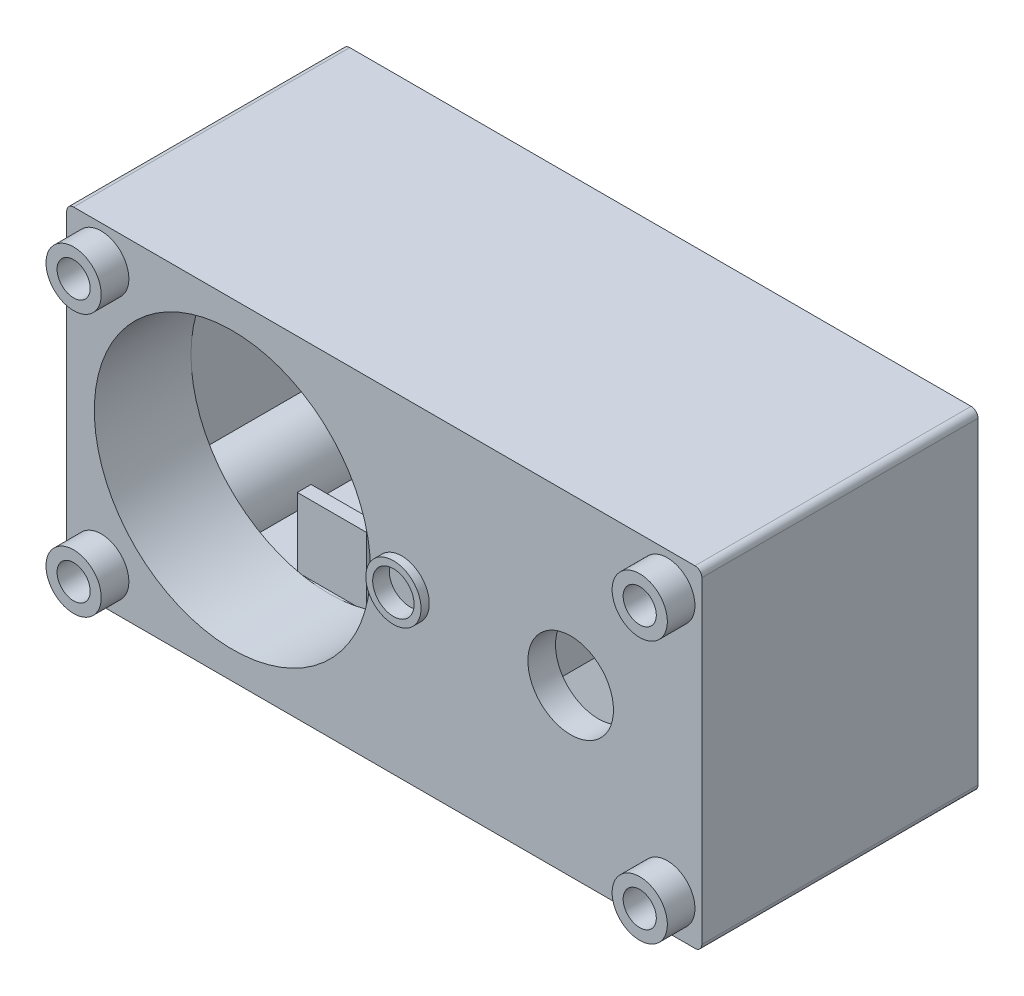
SolidWorks part; units mm, degrees
ref_plane "前视基准面" through (0, 0, 0) normal (0, 0, 1) x (1, 0, 0)
ref_plane "上视基准面" through (0, 0, 0) normal (0, 1, 0) x (1, 0, 0)
ref_plane "右视基准面" through (0, 0, 0) normal (1, 0, 0) x (0, 0, -1)
sketch "草图1" plane through (0, 0, 0) normal (0, 0, 1) x (1, 0, 0)
  line L0 (0, 0) -> (0, -8.3298) construction
  line L1 (-11.5, -6) -> (11.5, -6)
  line L2 (-11.5, -6) -> (-11.5, 6)
  line L3 (-11.5, 6) -> (11.5, 6)
  line L4 (11.5, -6) -> (11.5, 6)
  line L5 (-11.5, -6) -> (11.5, 6) construction
  line L6 (-11.5, 6) -> (11.5, -6) construction
  circle A0 centre (-10.25, 4.75) radius 0.6
  circle A1 centre (-10.25, -4.75) radius 0.6
  circle A2 centre (10.25, -4.75) radius 0.6
  circle A3 centre (10.25, 4.75) radius 0.6
  point P0 (0, 0)
  dimension "D3" = 1.2
  dimension "D1" = 23
  dimension "D2" = 12
  dimension "D4" = 1.25
  dimension "D5" = 1.25
  dimension "D6" = 1.25
extrude "凸台-拉伸1" add sketch "草图1" along normal blind 10 contours A0 | A1 | A3 | L1 L4 L3 L2 | A2 region at (-10.25, 4.75, 0) region at (-10.25, -4.75, 0) region at (10.25, 4.75, 0)
shell "抽壳2" thickness 1 removed face at (9.65, -4.75, 0)
extrude "拉伸-薄壁1" add sketch "草图1<3>" along normal blind 1 from offset 10 thin contours A0 | A1 | A2 | A3 thin type one direction wall 0.4
sketch "草图1<3>" plane through (0, 0, 0) normal (0, 0, 1) x (1, 0, 0) same geometry as "草图1"
sketch "草图2" plane through (0, 0, 10) normal (0, 0, 1) x (1, 0, 0)
  line L0 (11.5, -6) -> (11.5, 6) construction
  line L1 (-11.5, -6) -> (-11.5, 6) construction
  circle A0 centre (-5.5, 0) radius 5
  circle A1 centre (6.75, 0) radius 1.55
  circle A3 centre (0.63, 0) radius 0.75
  dimension "D1" = 3.1
  dimension "D3" = 10
  dimension "D5" = 1.5
  dimension "D2" = 4.75
  dimension "D4" = 6
  dimension "D6" = 6.13
extrude "切除-拉伸1" cut sketch "草图2" against normal up to next contours A0 | A1 region at (-5.5, 0, 10) region at (6.75, 0, 10)
extrude "拉伸-薄壁2" add sketch "草图2<3>" along normal blind 0.3 thin contours A3 thin type one direction wall 0.25
sketch "草图2<3>" plane through (0, 0, 10) normal (0, 0, 1) x (1, 0, 0) same geometry as "草图2"
extrude "切除-拉伸2" cut sketch "草图2<4>" against normal blind 0.3 contours A3
sketch "草图2<4>" plane through (0, 0, 10) normal (0, 0, 1) x (1, 0, 0) same geometry as "草图2"
sketch "草图3" plane through (0, 0, 9) normal (0, 0, -1) x (-1, 0, 0)
  line L0 (-4.575, 5) -> (-2.95, 3.375)
  line L1 (8.6697, 5) -> (-8.6697, 5) construction
  line L2 (-2.95, 3.375) -> (-2.95, -3.375)
  line L3 (-2.95, -3.375) -> (-4.575, -5)
  line L4 (5.5, -5) -> (-8.6697, -5) construction
  line L5 (-10.5, -3.1697) -> (-10.5, 3.1697) construction
  dimension "D1" = 7.55
  dimension "D2" = 135
  dimension "D3" = 135
  dimension "D4" = 6.75
extrude "拉伸-薄壁3" add sketch "草图3" along normal blind 5 thin thin type one direction reverse wall 0.5
sketch "草图4" plane through (0, 0, 9) normal (0, 0, -1) x (-1, 0, 0)
  circle A0 centre (5.5, 0) radius 5 construction
  circle A1 centre (5.5, 0) radius 5
extrude "拉伸-薄壁4" add sketch "草图4" along normal blind 2.5 thin thin type one direction wall 0.5
sketch "草图5" plane through (0, 0, 10) normal (0, 0, 1) x (1, 0, 0)
  line L0 (-5.5, 5) -> (-7.7913, 5) construction
  line L1 (-6.75, 5) -> (-4.25, 5)
  line L2 (-6.75, 5) -> (-6.75, 2.5)
  line L3 (-6.75, 2.5) -> (-4.25, 2.5)
  line L4 (-4.25, 5) -> (-4.25, 2.5)
  line L5 (-11.5, 0) -> (-2.2269, 0) construction
  line L6 (-11.5, -6) -> (-11.5, 6) construction
  line L7 (-4.25, -5) -> (-4.25, -2.5)
  line L8 (-6.75, -2.5) -> (-4.25, -2.5)
  line L9 (-6.75, -5) -> (-6.75, -2.5)
  line L10 (-6.75, -5) -> (-4.25, -5)
  circle A0 centre (-5.5, 0) radius 5 construction
  point P6 (-5.5, 5)
  dimension "D1" = 2.5
extrude "凸台-拉伸2" add sketch "草图5" against normal blind 0.5 from offset 3.6 offset against normal yes
fillet "圆角1" radius 0.25 4 edges at (11.5, 6, 5) (-11.5, 6, 5) (-11.5, -6, 5) (11.5, -6, 5)
